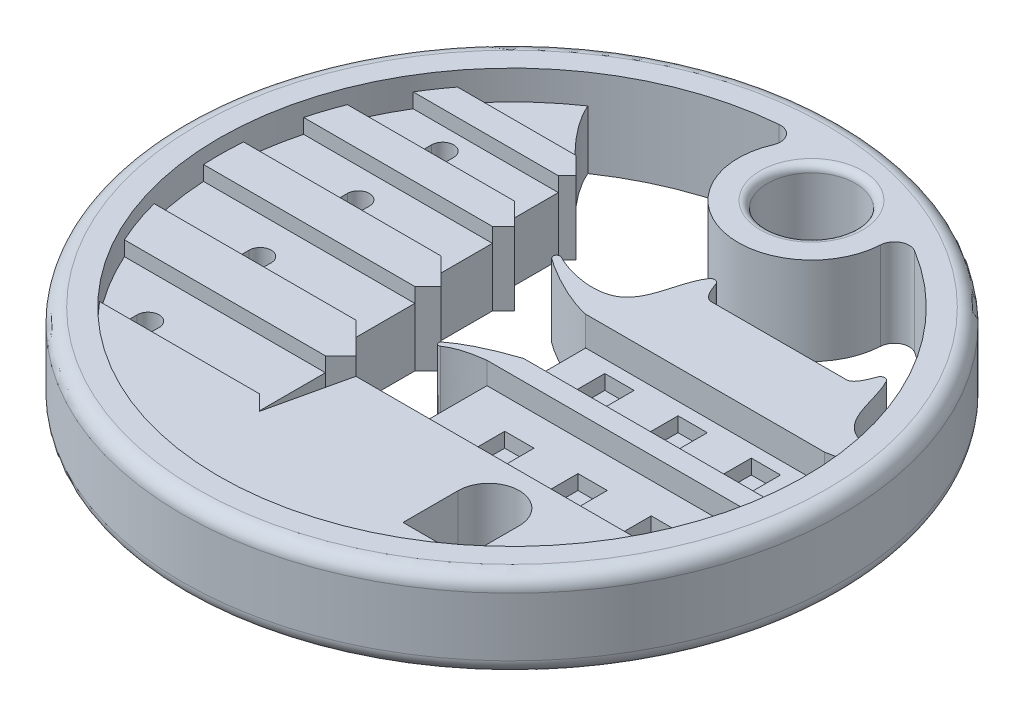
SolidWorks part; units mm, degrees
ref_plane "前视基准面" through (0, 0, 0) normal (0, 0, 1) x (1, 0, 0)
ref_plane "上视基准面" through (0, 0, 0) normal (0, 1, 0) x (1, 0, 0)
ref_plane "右视基准面" through (0, 0, 0) normal (1, 0, 0) x (0, 0, -1)
other "Configuration Table"
sketch "草图1" plane through (0, 0, 0) normal (0, 1, 0) x (1, 0, 0)
  circle A0 centre (0, 0) radius 22.5
  circle A1 centre (0, 0) radius 20
  dimension "D1" = 45
  dimension "D2" = 40
extrude "凸台-拉伸1" add sketch "草图1" along normal blind 6
sketch "草图2" plane through (0, 0, 0) normal (0, 1, 0) x (1, 0, 0)
  line L0 (-7.7984, 12.1607) -> (-6.5984, 10.9607)
  line L1 (-6.5984, 10.9607) -> (-7.1984, 10.3607)
  line L2 (-7.1984, 10.3607) -> (-7.1984, 7.3607)
  line L3 (-7.1984, 7.3607) -> (-5.6984, 5.8607)
  line L4 (-5.6984, 5.8607) -> (-6.4484, 5.1107)
  line L5 (-6.4484, 5.1107) -> (-6.4484, 1.6107)
  line L6 (-6.4484, 1.6107) -> (-4.6484, -0.1893)
  line L7 (-4.6484, -0.1893) -> (-5.5484, -1.0893)
  line L8 (-5.5484, -1.0893) -> (-5.5484, -5.0893)
  line L9 (-5.5484, -5.0893) -> (-3.4484, -7.1893)
  line L10 (-3.4484, -7.1893) -> (-4.4984, -8.2393)
  line L11 (-4.4984, -8.2393) -> (-4.4984, -12.7393)
  line L12 (-4.4984, -12.7393) -> (-2.0984, -15.1393)
  line L13 (-2.0984, -15.1393) -> (-3.2984, -16.3393)
  line L14 (-3.2984, -16.3393) -> (-3.2984, -21.3393)
  line L15 (-14.3494, 1.6107) -> (-12.8494, 1.6107)
  line L16 (-14.3494, 7.3607) -> (-12.8494, 7.3607)
  line L17 (-14.3494, 7.3607) -> (-14.3494, 8.8607)
  line L19 (-12.8494, 7.3607) -> (-12.8494, 8.8607)
  line L20 (-14.3494, 1.6107) -> (-14.3494, 3.1107)
  line L21 (-12.8494, 1.6107) -> (-12.8494, 3.1107)
  line L22 (-14.3494, -5.0893) -> (-12.8494, -5.0893)
  line L23 (-14.3494, -5.0893) -> (-14.3494, -3.5893)
  line L24 (-12.8494, -5.0893) -> (-12.8494, -3.5893)
  line L25 (-14.3494, -12.7393) -> (-12.8494, -12.7393)
  line L26 (-14.3494, -12.7393) -> (-14.3494, -11.2393)
  line L27 (-12.8494, -12.7393) -> (-12.8494, -11.2393)
  circle A0 centre (0, 0) radius 21.5927
  arc A1 (-12.8494, 8.8607) -> (-14.3494, 8.8607) centre (-13.5994, 8.8607) ccw
  arc A2 (-12.8494, 3.1107) -> (-14.3494, 3.1107) centre (-13.5994, 3.1107) ccw
  arc A3 (-12.8494, -3.5893) -> (-14.3494, -3.5893) centre (-13.5994, -3.5893) ccw
  arc A4 (-12.8494, -11.2393) -> (-14.3494, -11.2393) centre (-13.5994, -11.2393) ccw
  spline S0 degree 3 poles (-7.7984, 12.1607) (-7.7984, 12.1607) (-7.9196, 12.2819) (-11.8411, 15.6134) (-11.6565, 18.1762) knots 0 0 0 0 0.05 1 1 1 1
  dimension "D17" = 1.5
  dimension "D19" = 1.5
  dimension "D25" = 0
  dimension "D1" = 3
  dimension "D2" = 3.5
  dimension "D3" = 4
  dimension "D4" = 4.5
  dimension "D5" = 5
  dimension "D6" = 135
  dimension "D7" = 1.5
  dimension "D8" = 0.75
  dimension "D9" = 1.8
  dimension "D10" = 0.9
  dimension "D11" = 2.1
  dimension "D12" = 1.05
  dimension "D13" = 2.4
  dimension "D14" = 1.2
  dimension "D15" = 0.6
  dimension "D16" = 1.2
  dimension "D18" = 1.5
  dimension "D20" = 1.5
  dimension "D21" = 1.5
  dimension "D22" = 1.5
  dimension "D23" = 1.5
  dimension "D24" = 1.5
extrude "凸台-拉伸2" add sketch "草图2" along normal blind 4 contours L0 S0 A0 L14 L13 L12 L11 L10 L9 L8 L7 L6 L5 L4 L3 L2 L1 region at (-12.226, 0, 2.4221)
sketch "草图3" plane through (0, 0, 0) normal (0, 1, 0) x (1, 0, 0)
  line L0 (14.6317, -15.4435) -> (-3.8439, -15.4435)
  line L1 (-3.8439, -15.4435) -> (-2.2446, -8.4123)
  line L2 (-2.2446, -8.4123) -> (19.8143, -8.4123)
  line L3 (19.8143, -8.4123) -> (14.6317, -15.4435)
  line L4 (10.0844, -8.419) -> (10.0844, -13.7531) construction
  line L5 (8.0031, -15.4435) -> (12.1657, -15.4435)
  line L6 (8.0031, -15.4435) -> (8.0031, -11.6731)
  line L8 (12.1657, -15.4435) -> (12.1657, -11.6731)
  line L9 (0.7823, -8.4123) -> (0.7823, -2.4903)
  line L10 (1.9261, -1.1298) -> (1.9261, 3.1063)
  line L11 (5.4662, 8.1308) -> (14.7026, 8.1308)
  line L12 (1.9261, 3.1063) -> (18.2428, 3.1063)
  line L13 (0.7823, -2.4903) -> (19.3866, -2.4903)
  line L14 (1.9261, -1.1298) -> (18.2428, -1.1298)
  line L16 (20.145, 4.948) -> (20.4973, 3.7589)
  line L19 (-3.8439, -15.4435) -> (-3.8439, -20.7229)
  line L20 (-3.8439, -20.7229) -> (1.0329, -21.162)
  line L21 (1.0329, -21.162) -> (7.1573, -19.7754)
  line L22 (7.1573, -19.7754) -> (11.687, -18.0832)
  line L23 (11.687, -18.0832) -> (14.6317, -15.4435)
  line L24 (18.2428, -1.1298) -> (18.2428, 3.1063)
  line L25 (19.3866, -8.4123) -> (19.3866, -2.4903)
  arc A0 (12.1657, -11.6731) -> (8.0031, -11.6731) centre (10.0844, -11.6731) ccw
  arc A1 (-1.8467, -2.954) -> (-1.635, -3.242) centre (-1.7377, -3.0957) ccw
  arc A2 (-2.2753, 5.6433) -> (-2.5399, 5.2532) centre (-2.3866, 5.434) ccw
  arc A3 (4.0307, 9.4268) -> (4.5698, 9.3567) centre (4.2825, 9.2557) cw
  arc A4 (16.1543, 9.4001) -> (15.5991, 9.3567) centre (15.8863, 9.2557) ccw
  arc A6 (22.0155, -2.954) -> (21.8038, -3.242) centre (21.9065, -3.0957) cw
  spline S0 degree 3 poles (4.0307, 9.4268) (3.123, 8.0907) (3.4273, 4.257) (-1.0474, 4.9899) (-2.2753, 5.6433) knots 0 0 0 0 0.619573 1 1 1 1
  spline S1 degree 3 poles (-2.5399, 5.2532) (-2.2349, 4.9946) (0.0082, 3.5069) (1.9261, 3.1063) knots 0 0 0 0 1 1 1 1
  spline S2 degree 2 poles (1.9261, -1.1298) (-0.5164, -1.9306) (-1.8467, -2.954) knots 0 0 0 1 1 1
  spline S3 degree 2 poles (0.7823, -2.4903) (-0.8163, -2.6678) (-1.635, -3.242) knots 0 0 0 1 1 1
  spline S4 degree 3 poles (4.5698, 9.3567) (4.7092, 8.9603) (5.0082, 8.1308) (5.4662, 8.1308) knots 0 0 0 0 1 1 1 1
  spline S5 degree 3 poles (15.5991, 9.3567) (15.4596, 8.9603) (15.1607, 8.1308) (14.7026, 8.1308) knots 0 0 0 0 1 1 1 1
  spline S6 degree 2 poles (19.3866, -2.4903) (20.9852, -2.6678) (21.8038, -3.242) knots 0 0 0 1 1 1
  spline S7 degree 2 poles (18.2428, -1.1298) (20.6852, -1.9306) (22.0155, -2.954) knots 0 0 0 1 1 1
  spline S8 degree 3 poles (20.4973, 3.7589) (19.7998, 3.3821) (18.9702, 3.2583) (18.2428, 3.1063) knots 0.620727 0.620727 0.620727 0.620727 1 1 1 1
  spline S9 degree 3 poles (16.1543, 9.4001) (16.9205, 7.9781) (16.8674, 5.0968) (19.5553, 4.894) (20.145, 4.948) knots 0 0 0 0 0.619573 0.781574 0.781574 0.781574 0.781574
extrude "凸台-拉伸3" add sketch "草图3" along normal blind 5 contours L4 L11 S4 A3 S0 A2 S1 L12 | L11 L4 L12 | L4 L2 L1 L0 L6 A0 | L2 L4 A0 L8 L0 L3 | L4 L5 L0 L19 L20 L21 L22 | L0 L4 L22 L23 region at (3.6236, 0, 17.8128) region at (6.5872, 0, 11.6562) region at (9.8512, 0, -5.5019)
extrude "凸台-拉伸5" add sketch "草图3<4>" along normal blind 4.5 contours L4 L14 S2 A1 S3 L13 | L14 L4 L13 region at (10.0844, 0, 1.8899)
sketch "草图3<4>" plane through (0, 0, 0) normal (0, 1, 0) x (1, 0, 0) same geometry as "草图3"
extrude "凸台-拉伸6" add sketch "草图3<5>" along normal blind 3 contours L4 L12 L10 L14 | L12 L4 L14 | L4 L13 L9 L2 | L13 L4 L2 region at (10.0844, 0, 5.4513) region at (10.0844, 0, -0.9882)
sketch "草图3<5>" plane through (0, 0, 0) normal (0, 1, 0) x (1, 0, 0) same geometry as "草图3"
sketch "草图4" plane through (0, 3, 0) normal (0, 1, 0) x (1, 0, 0)
  line L0 (10.0844, 199991.581) -> (10.0844, -200013.7531) construction
  line L1 (4.0844, 2.2516) -> (6.0844, 2.2516)
  line L2 (4.0844, 2.2516) -> (4.0844, 0.2516)
  line L3 (4.0844, 0.2516) -> (6.0844, 0.2516)
  line L4 (6.0844, 2.2516) -> (6.0844, 0.2516)
  line L5 (11.0844, 2.2516) -> (9.0844, 2.2516)
  line L6 (11.0844, 2.2516) -> (11.0844, 0.2516)
  line L7 (11.0844, 0.2516) -> (9.0844, 0.2516)
  line L8 (9.0844, 2.2516) -> (9.0844, 0.2516)
  line L9 (14.0844, 2.2516) -> (16.0844, 2.2516)
  line L10 (14.0844, 2.2516) -> (14.0844, 0.2516)
  line L11 (14.0844, 0.2516) -> (16.0844, 0.2516)
  line L12 (16.0844, 2.2516) -> (16.0844, 0.2516)
  line L13 (4.0844, -4.5802) -> (6.0844, -4.5802)
  line L14 (4.0844, -4.5802) -> (4.0844, -6.5802)
  line L15 (4.0844, -6.5802) -> (6.0844, -6.5802)
  line L16 (6.0844, -4.5802) -> (6.0844, -6.5802)
  line L17 (11.0844, -4.5802) -> (9.0844, -4.5802)
  line L18 (11.0844, -4.5802) -> (11.0844, -6.5802)
  line L19 (11.0844, -6.5802) -> (9.0844, -6.5802)
  line L20 (9.0844, -4.5802) -> (9.0844, -6.5802)
  line L21 (14.0844, -4.5802) -> (16.0844, -4.5802)
  line L22 (14.0844, -4.5802) -> (14.0844, -6.5802)
  line L23 (14.0844, -6.5802) -> (16.0844, -6.5802)
  line L24 (16.0844, -4.5802) -> (16.0844, -6.5802)
  point P13 (10.0844, 0.2516)
  dimension "D1" = 2
  dimension "D2" = 2
  dimension "D3" = 2
  dimension "D4" = 2
  dimension "D5" = 2
  dimension "D6" = 2
  dimension "D7" = 3
  dimension "D8" = 3
  dimension "D9" = 2
  dimension "D10" = 2
  dimension "D11" = 2
  dimension "D12" = 2
  dimension "D13" = 2
  dimension "D14" = 3
  dimension "D15" = 3
  dimension "D16" = 2
extrude "切除-拉伸1" cut sketch "草图4" against normal blind 1
sketch "草图5" plane through (0, 0, 0) normal (0, 1, 0) x (1, 0, 0)
  circle A0 centre (3.901, 16.5464) radius 3
  circle A1 centre (3.901, 16.5464) radius 5
  circle A2 centre (0, 0) radius 20 construction
  dimension "D1" = 6
  dimension "D2" = 10
extrude "凸台-拉伸7" add sketch "草图5" along normal blind 6
fillet "圆角1" radius 1 2 edges at (0.2834, 3, -19.998) (8.6793, 3, -18.0186)
sketch "草图6" plane through (0, 4, 0) normal (0, 1, 0) x (1, 0, 0)
  line L0 (-7.7984, 12.1607) -> (-16.9288, 12.1607)
  line L1 (-7.1984, 10.3607) -> (-18.3154, 10.3607)
  line L2 (-7.1984, 7.3607) -> (-18.8932, 7.3607)
  line L3 (-6.4484, 5.1107) -> (-20.1643, 5.1107)
  line L4 (-6.4484, 1.6107) -> (-20.5035, 1.6107)
  line L5 (-5.5484, -1.0893) -> (-20.6953, -1.0893)
  line L6 (-5.5484, -5.0893) -> (-20.1643, -5.0893)
  line L7 (-4.4984, -8.2393) -> (-18.8932, -8.2393)
  line L8 (-4.4984, -12.7393) -> (-16.1866, -12.7393)
  line L9 (-16.9288, 12.1607) -> (-18.3154, 10.3607)
  line L10 (-18.8932, 7.3607) -> (-20.1643, 5.1107)
  line L11 (-20.6953, -1.0893) -> (-20.5035, 1.6107)
  line L12 (-20.1643, -5.0893) -> (-18.8932, -8.2393)
  line L14 (-4.4984, -12.7393) -> (-1.4692, -15.7685)
  line L15 (-1.4692, -15.7685) -> (-0.3655, -21.0674)
  line L16 (-16.1866, -12.7393) -> (-12.7105, -15.7685)
  line L17 (-12.7105, -15.7685) -> (-7.7984, -19.2359)
  line L18 (-7.7984, -19.2359) -> (-3.123, -21.6418)
  line L19 (-3.123, -21.6418) -> (-0.3655, -21.0674)
  line M2 (-3.4641, -13.7736) -> (-4.4984, -12.7393)
  line M4 (-4.4984, -8.2393) -> (-3.4484, -7.1893)
  line M5 (-3.4484, -7.1893) -> (-5.5484, -5.0893)
  line M7 (-5.5484, -1.0893) -> (-4.6484, -0.1893)
  line M8 (-4.6484, -0.1893) -> (-6.4484, 1.6107)
  line M10 (-6.4484, 5.1107) -> (-5.6984, 5.8607)
  line M11 (-5.6984, 5.8607) -> (-7.1984, 7.3607)
  line M13 (-7.1984, 10.3607) -> (-6.5984, 10.9607)
  line M14 (-6.5984, 10.9607) -> (-7.7984, 12.1607)
  arc M16 (-11.314, 16.4922) -> (-3.8439, -19.6271) centre (0, 0) ccw
  line M20 (-12.8494, -12.7393) -> (-14.3494, -12.7393)
  line M24 (-12.8494, -5.0893) -> (-14.3494, -5.0893)
  line M28 (-12.8494, 1.6107) -> (-14.3494, 1.6107)
  line M32 (-12.8494, 7.3607) -> (-14.3494, 7.3607)
  line M51 (-3.8439, -15.4435) -> (-3.4641, -13.7736)
  line M52 (-3.8439, -19.6271) -> (-3.8439, -15.4435)
extrude "凸台-拉伸8" add sketch "草图6" along normal blind 1 contours L1 L0 M13 M14 M16 | L3 L2 M10 M11 M32 M16 | L5 L4 M7 M8 M28 M16 | L7 L6 M4 M5 M24 M16 | L8 M2 M20 M16 M52 M51 region at (-11.8084, 4, -11.2273) region at (-8.1389, 4, 15.361) region at (-11.5698, 4, 6.6716) region at (-12.6823, 4, -0.2401) region at (-12.6521, 4, -6.2087)
fillet "圆角2" radius 0.5 2 edges at (3.901, 6, -13.5464) (3.901, 0, -13.5464)
fillet "圆角3" radius 1 2 edges at (0, 0, 22.5) (0, 6, 22.5)
